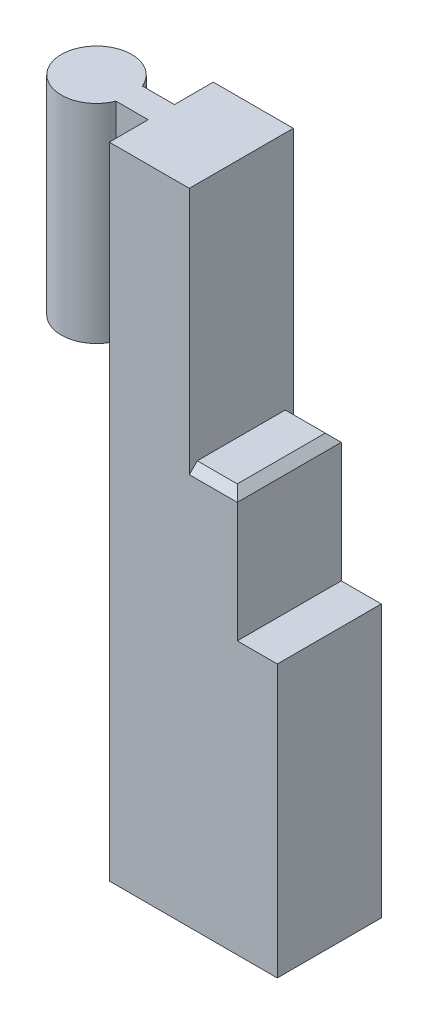
SolidWorks part; units mm, degrees
ref_plane "Płaszczyzna przednia" through (0, 0, 0) normal (0, 0, 1) x (1, 0, 0)
ref_plane "Płaszczyzna górna" through (0, 0, 0) normal (0, 1, 0) x (1, 0, 0)
ref_plane "Płaszczyzna prawa" through (0, 0, 0) normal (1, 0, 0) x (0, 0, -1)
sketch "Szkic1" plane through (0, 0, 0) normal (0, 0, 1) x (1, 0, 0)
  line L1 (-5.25, 20) -> (5.25, 20)
  line L2 (-5.25, 20) -> (-5.25, -20)
  line L3 (-5.25, -20) -> (5.25, -20)
  line L4 (5.25, 20) -> (5.25, -20)
  line L5 (-5.25, 20) -> (5.25, -20) construction
  line L6 (-5.25, -20) -> (5.25, 20) construction
  point P0 (0, 0)
  dimension "D1" = 10.5
  dimension "D2" = 40
extrude "Dodanie-wyciągnięcie1" add sketch "Szkic1" along normal blind 6.5
sketch "Szkic2" plane through (0, 0, 6.5) normal (0, 0, 1) x (1, 0, 0)
  line L0 (-0.25, 20) -> (-0.25, 5)
  line L1 (5.25, 20) -> (-5.25, 20) construction
  line L2 (-0.25, 5) -> (5.25, 5)
  line L3 (5.25, -20) -> (5.25, 20) construction
  line L4 (5.25, 5) -> (5.25, 20)
  line L5 (5.25, 20) -> (-0.25, 20)
  line L6 (-5.25, 20) -> (-5.25, -20) construction
  line L8 (2.75, 5) -> (5.25, 5)
  line L9 (2.75, 5) -> (2.75, -3)
  line L10 (2.75, -3) -> (5.25, -3)
  line L11 (5.25, 5) -> (5.25, -3)
  line M6 (5.25, -20) -> (5.25, 20)
  line M7 (5.25, 20) -> (-5.25, 20)
  dimension "5" = 5
  dimension "D2" = 15
  dimension "D3" = 8
  dimension "D4" = 8
extrude "Wytnij-wyciągnięcie1" cut sketch "Szkic2" against normal blind 6.5 contours L9 L10 L2 M6 | L0 L2 M6 M7 region at (2.5, 12.5, 6.5) region at (4, 1, 6.5)
chamfer "Sfazowanie1" distance 0.5 angle 45 3 edges at (1.25, 5, 0) (2.75, 5, 3.25) (1.25, 5, 6.5)
sketch "Szkic3" plane through (0, 20, 0) normal (0, 1, 0) x (1, 0, 0)
  line L0 (-5.25, -3.25) -> (-9.3, -3.25) construction
  line L1 (-5.25, -6.5) -> (-5.25, 0) construction
  line L3 (-5.25, -4.0704) -> (-9.3, -4.0704)
  line L4 (-5.25, -4.0704) -> (-5.25, -2.4296)
  line L5 (-5.25, -2.4296) -> (-9.3, -2.4296)
  line L6 (-9.3, -4.0704) -> (-9.3, -2.4296)
  line L7 (-5.25, -4.0704) -> (-9.3, -2.4296) construction
  line L8 (-5.25, -2.4296) -> (-9.3, -4.0704) construction
  circle A0 centre (-9.3, -3.25) radius 2.2
  point P5 (-7.275, -3.25)
  line M10 (-5.25, 0) -> (-5.25, -6.5)
  dimension "D2" = 4.4
  dimension "D1" = 4.05
extrude "Dodanie-wyciągnięcie2" add sketch "Szkic3" against normal blind 13 contours L5 A0 L3 L6 | L3 A0 L5 L6 | A0 L3 L5 M10 region at (-6.2016, 20, 3.25) region at (-9.6242, 20, 3.25) region at (-8.2255, 20, 3.25)
